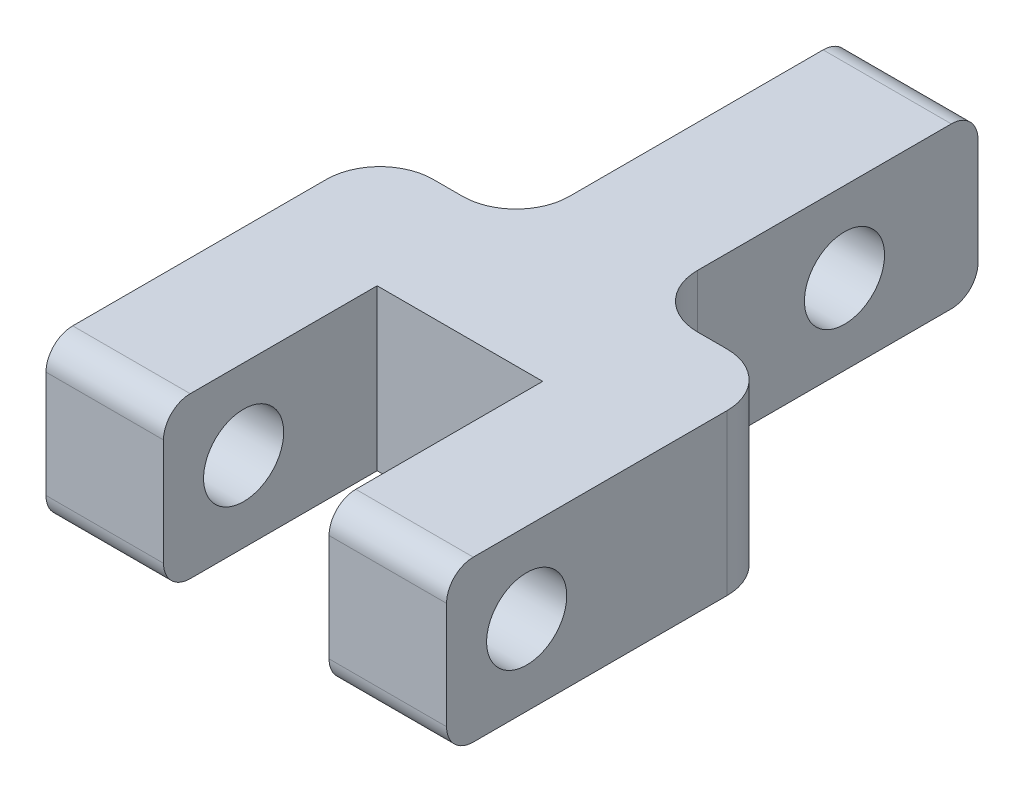
SolidWorks part; units mm, degrees
ref_plane "Alzado" through (0, 0, 0) normal (0, 0, 1) x (1, 0, 0)
ref_plane "Planta" through (0, 0, 0) normal (0, 1, 0) x (1, 0, 0)
ref_plane "Vista lateral" through (0, 0, 0) normal (1, 0, 0) x (0, 0, -1)
sketch "Croquis1" plane through (0, 0, 0) normal (1, 0, 0) x (0, 0, -1)
  line L0 (-11.5, 3) -> (11.5, 3)
  line L2 (-12.5, 0) -> (12.5, 0) construction
  line L3 (-12.5, 2) -> (-12.5, -2)
  line L4 (-11.5, -3) -> (11.5, -3)
  line L5 (12.5, 2) -> (12.5, -2)
  arc A0 (-12.5, -2) -> (-11.5, -3) centre (-11.5, -2) ccw
  arc A1 (-12.5, 2) -> (-11.5, 3) centre (-11.5, 2) cw
  arc A2 (11.5, -3) -> (12.5, -2) centre (11.5, -2) ccw
  arc A3 (11.5, 3) -> (12.5, 2) centre (11.5, 2) cw
  point P1 (0, 0)
  point P9 (-12.5, -3)
  point P13 (-12.5, 3)
  point P16 (12.5, -3)
  point P19 (12.5, 3)
  dimension "D3" = 1
  dimension "D4" = 1
  dimension "D1" = 3
  dimension "D2" = 25
extrude "Saliente-Extruir1" add sketch "Croquis1" along normal mid plane 4.8
sketch "Croquis2" plane through (0, 0, 0) normal (1, 0, 0) x (0, 0, -1)
  line L0 (-12.5, 2) -> (-12.5, -2) construction
  line L1 (12.5, -2) -> (12.5, 2) construction
  circle A0 centre (-9.5, 0) radius 1.5
  circle A1 centre (7.5, 0) radius 1.5
  dimension "D1" = 3
  dimension "D3" = 3
  dimension "D2" = 3
  dimension "D4" = 5
extrude "Cortar-Extruir1" cut sketch "Croquis2" against normal through all both and the other way through all
sketch "Croquis3" plane through (0, 0, 0) normal (1, 0, 0) x (0, 0, -1)
  line L0 (-12.5, 2) -> (-12.5, -2) construction
  line L1 (-12.5, 2) -> (-12.5, -2)
  line L2 (-11.5, 3) -> (0, 3)
  line L3 (11.5, 3) -> (-11.5, 3) construction
  line L4 (0, 3) -> (0, -3)
  line L5 (-11.5, -3) -> (11.5, -3) construction
  line L6 (0, -3) -> (-11.5, -3)
  circle A0 centre (-9.5, 0) radius 1.5 construction
  circle A1 centre (-9.5, 0) radius 1.5
  arc A2 (-11.5, 3) -> (-12.5, 2) centre (-11.5, 2) ccw construction
  arc A3 (-11.5, 3) -> (-12.5, 2) centre (-11.5, 2) ccw
  arc A4 (-12.5, -2) -> (-11.5, -3) centre (-11.5, -2) ccw construction
  arc A5 (-12.5, -2) -> (-11.5, -3) centre (-11.5, -2) ccw
extrude "Saliente-Extruir2" add sketch "Croquis3" along normal mid plane 15
sketch "Croquis4" plane through (0, 0, 0) normal (1, 0, 0) x (0, 0, -1)
  line L0 (-11.5, 3) -> (-4.5, 3)
  line L1 (0, 3) -> (-11.5, 3) construction
  line L2 (-4.5, 3) -> (-4.5, -3)
  line L3 (-11.5, -3) -> (0, -3) construction
  line L4 (-12.5, 2) -> (-12.5, -2)
  line L5 (-11.5, -3) -> (0, -3)
  line L6 (0, -3) -> (0, 3)
  line L7 (0, 3) -> (-11.5, 3)
  line L8 (-12.5, 2) -> (-12.5, -2)
  line L12 (-4.5, -3) -> (-11.5, -3)
  arc A2 (-11.5, 3) -> (-12.5, 2) centre (-11.5, 2) ccw
  arc A3 (-12.5, -2) -> (-11.5, -3) centre (-11.5, -2) ccw
  arc A4 (-11.5, 3) -> (-12.5, 2) centre (-11.5, 2) ccw
  arc A5 (-12.5, -2) -> (-11.5, -3) centre (-11.5, -2) ccw
  dimension "D2" = 8
  dimension "D1" = 0
extrude "Cortar-Extruir2" cut sketch "Croquis4" against normal mid plane 6.2
fillet "Redondeo1" radius 2 4 edges at (2.4, 0, 0) (-2.4, 0, 0) (7.5, 0, 0) (-7.5, 0, 0)
